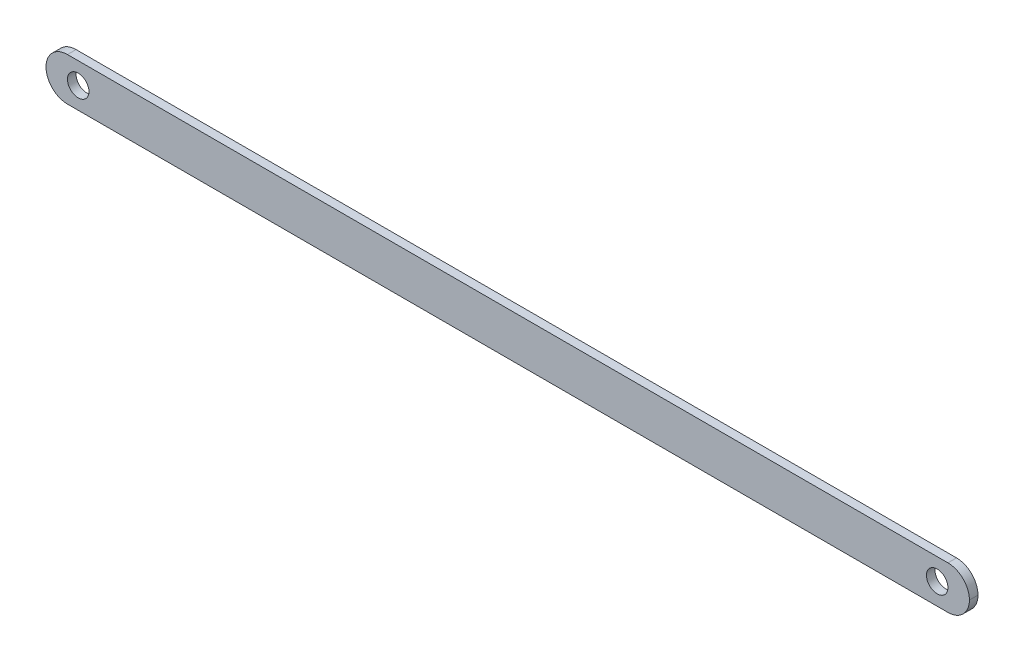
SolidWorks part; units mm, degrees
note: The reader was unsure of these and kept them because the rebuilt part matched: thickness of "Базовая кромка1", "Листовой металл7", "Листовой металл8".
material "6063-T6"
ref_plane "Спереди" through (0, 0, 0) normal (0, 0, 1) x (1, 0, 0)
ref_plane "Сверху" through (0, 0, 0) normal (0, 1, 0) x (1, 0, 0)
ref_plane "Справа" through (0, 0, 0) normal (1, 0, 0) x (0, 0, -1)
sketch "Эскиз1" plane through (0, 0, 0) normal (0, 0, 1) x (1, 0, 0)
  line L1 (107.5, -5) -> (-107.5, -5)
  line L2 (107.5, -5) -> (107.5, 5)
  line L3 (107.5, 5) -> (-107.5, 5)
  line L4 (-107.5, -5) -> (-107.5, 5)
  line L5 (107.5, -5) -> (-107.5, 5) construction
  line L6 (107.5, 5) -> (-107.5, -5) construction
  point P0 (0, 0)
  dimension "D1" = 215
  dimension "D2" = 10
base flange "Базовая кромка1" sketch "Эскиз1" thickness 2 reverse thickness direction no parameters "D1"=2
sketch "Эскиз6" plane through (0, 0, 0) normal (0, 0, 1) x (1, 0, 0)
  line L0 (0, 0) -> (0, 5) construction
  line L1 (107.5, -5) -> (-107.5, 5) construction
  line L2 (107.5, 5) -> (-107.5, 5) construction
  line L3 (0, 0) -> (107.5, 0) construction
  line L4 (107.5, -5) -> (107.5, 5) construction
  circle A0 centre (100, 0) radius 2.5
  circle A1 centre (-100, 0) radius 2.5
  dimension "D1" = 5
  dimension "D2" = 200
extrude "Вырез-Вытянуть1" cut sketch "Эскиз6" against normal through all normal cut yes
fillet "Скругление1" radius 5 4 edges at (107.5, -5, -1) (107.5, 5, -1) (-107.5, -5, -1) (-107.5, 5, -1)
sketch "Сгиб-Линии1" plane through (0, 0, 0) normal (0, 1, 0) x (1, 0, 0)
sketch "Граничная рамка1" plane through (0, 0, 0) normal (0, 1, 0) x (1, 0, 0)
sheet metal parameters "Листовой металл7" thickness 2 parameters "D1"=2, "D7"=0.5
flat pattern "Развертка7" [suppressed]
sketch "Сгиб-Линии2" plane through (0, 0, 0) normal (0, 1, 0) x (1, 0, 0)
sketch "Граничная рамка2" [suppressed] plane through (0, 0, 0) normal (0, 1, 0) x (1, 0, 0)
sheet metal parameters "Листовой металл8" thickness 2 parameters "D1"=2, "D7"=0.5
flat pattern "Развертка7"
sketch "Сгиб-Линии2" plane through (0, 0, 0) normal (0, 1, 0) x (1, 0, 0)
sketch "Граничная рамка2" [suppressed] plane through (0, 0, 0) normal (0, 1, 0) x (1, 0, 0)
